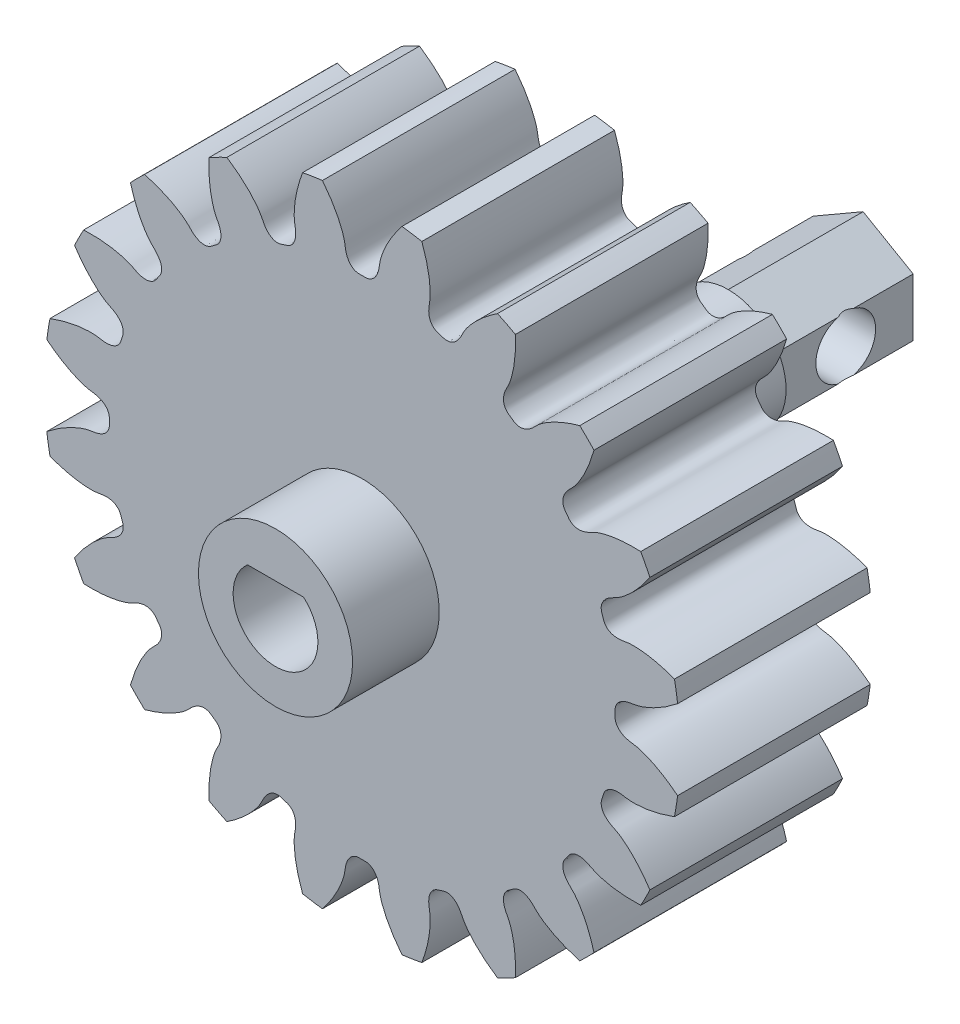
SolidWorks part; units mm, degrees
ref_plane "Front Plane" through (0, 0, 0) normal (0, 0, 1) x (1, 0, 0)
ref_plane "Top Plane" through (0, 0, 0) normal (0, 1, 0) x (1, 0, 0)
ref_plane "Right Plane" through (0, 0, 0) normal (1, 0, 0) x (0, 0, -1)
ref_axis "Axis1" through (0, 0, 55) along (0, 0, -1)
sketch "SketchRevolveSpurAssembly01Pinion" plane through (0, 0, 0) normal (1, 0, 0) x (0, 0, -1)
  line L0 (0, 0) -> (1, 0) construction
  line L1 (-5, 0) -> (-5, 16.5)
  line L2 (-5, 16.5) -> (5, 16.5)
  line L3 (5, 16.5) -> (5, 0)
  line L4 (5, 0) -> (-5, 0)
  dimension "Side1" = 5
  dimension "OutsideRadius" = 16.5
  dimension "Side2" = 5
revolve "SpurAssembly01Pinion" add sketch "SketchRevolveSpurAssembly01Pinion" angle 360 about L0
sketch "SketchToothSpurAssembly01Pinion" plane through (0, 0, 0) normal (0, 0, 1) x (1, 0, 0)
  arc A0 (16.4388, 2.1204) -> (16.4388, -2.1204) centre (0, 0) cw
  spline S0 degree 3 poles (16.4388, -2.1204) (16.3062, -2.0126) (16.1079, -1.8609) (15.8417, -1.6767) (15.6549, -1.5557) (15.4759, -1.4476) (15.3054, -1.3516) (15.1441, -1.2672) (14.9923, -1.1937) (14.8506, -1.1305) (14.7196, -1.0767) (14.5996, -1.0318) (14.491, -0.9949) (14.3942, -0.9653) (14.3096, -0.9423) (14.2375, -0.925) (14.178, -0.9126) (14.0492, -0.8903) (13.9123, -0.8782) (13.7697, -0.8427) (13.6956, -0.8206) (13.6244, -0.795) (13.5557, -0.7654) (13.4893, -0.7311) (13.4248, -0.6913) (13.3623, -0.6446) (13.3021, -0.5892) (13.2452, -0.523) (13.1943, -0.4439) (13.1533, -0.3509) (13.1303, -0.2534) (13.1208, -0.135) (13.1277, 0) (13.1208, 0.135) (13.1303, 0.2534) (13.1533, 0.3509) (13.1943, 0.4439) (13.2452, 0.523) (13.3021, 0.5892) (13.3623, 0.6446) (13.4248, 0.6913) (13.4893, 0.7311) (13.5557, 0.7654) (13.6244, 0.795) (13.6956, 0.8206) (13.7697, 0.8427) (13.9123, 0.8782) (14.0492, 0.8903) (14.178, 0.9126) (14.2375, 0.925) (14.3096, 0.9423) (14.3942, 0.9653) (14.491, 0.9949) (14.5996, 1.0318) (14.7196, 1.0767) (14.8506, 1.1305) (14.9923, 1.1937) (15.1441, 1.2672) (15.3054, 1.3516) (15.4759, 1.4476) (15.6549, 1.5557) (15.8417, 1.6767) (16.1079, 1.8609) (16.3062, 2.0126) (16.4388, 2.1204) knots 0 0 0 0 0.061423 0.08971 0.11638 0.141434 0.164872 0.186693 0.206898 0.225486 0.242459 0.257814 0.271554 0.283677 0.294183 0.303073 0.310347 0.316004 0.350077 0.359568 0.368803 0.377844 0.386769 0.395676 0.404689 0.413963 0.423683 0.434051 0.445256 0.457401 0.47042 0.481067 0.5 0.518933 0.52958 0.542599 0.554744 0.565949 0.576317 0.586037 0.595311 0.604324 0.613231 0.622156 0.631197 0.640432 0.649923 0.683996 0.689653 0.696927 0.705817 0.716323 0.728446 0.742186 0.757541 0.774514 0.793102 0.813307 0.835128 0.858566 0.88362 0.91029 0.938577 1 1 1 1
extrude "ToothExtrudeCutSpurAssembly01Pinion" cut sketch "SketchToothSpurAssembly01Pinion" against normal blind 5 and the other way blind 5
pattern_circular "PatternSpurAssembly01Pinion" count 20 every 18 about axis through (0, 0, 55) along (0, 0, -1) of "ToothExtrudeCutSpurAssembly01Pinion"
sketch "AuxiliarySketchSpurAssembly01Pinion" plane through (0, 0, 0) normal (0, 0, 1) x (1, 0, 0)
  circle A0 centre (0, 0) radius 15 construction
  circle A1 centre (0, 0) radius 14.0954 construction
  circle A2 centre (0, 0) radius 14.1048 construction
  circle A3 centre (0, 0) radius 16.5 construction
  circle A4 centre (0, 0) radius 13.125 construction
  dimension "PitchDiameter" = 30
  dimension "BaseDiameter" = 28.1908
  dimension "FormDiameter" = 28.2095
  dimension "MajorDiameter" = 33
  dimension "MinorDiameter" = 26.25
sketch "Sketch2" plane through (0, 0, -5) normal (0, 0, -1) x (-1, 0, 0)
  circle A0 centre (0, 0) radius 3
extrude "Boss-Extrude1" add sketch "Sketch2" along normal blind 9
sketch "Sketch3" plane through (0, 0, -14) normal (0, 0, -1) x (-1, 0, 0)
  line L0 (0, 3) -> (-2.5981, 1.5)
  line L1 (-2.5981, 1.5) -> (-2.5981, -1.5)
  line L2 (0, -3) -> (0, 3) construction
  line L3 (-2.5981, -1.5) -> (2.5981, 1.5) construction
  line L4 (2.5981, -1.5) -> (-2.5981, 1.5) construction
  line L5 (-2.5981, -1.5) -> (0, -3)
  line L6 (0, -3) -> (2.5981, -1.5)
  line L7 (2.5981, -1.5) -> (2.5981, 1.5)
  line L8 (2.5981, 1.5) -> (0, 3)
  circle A0 centre (0, 0) radius 3 construction
  point P11 (0, 0)
  point P15 (0, 0)
  point P18 (0, 0)
extrude "Boss-Extrude2" add sketch "Sketch3" along normal blind 7
sketch "Sketch4" plane through (2.5981, 0, 0) normal (1, 0, 0) x (0, 0, -1)
  line L0 (14, 1.5) -> (21, -1.5) construction
  circle A0 centre (17.5, 0) radius 1.55
extrude "Cut-Extrude3" cut sketch "Sketch4" against normal up to surface (5.1962 mm away) up to face at (-2.5981, 0, -17.5)
sketch "Sketch5" plane through (0, 0, 5) normal (0, 0, 1) x (1, 0, 0)
  circle A0 centre (0, 0) radius 4
extrude "Boss-Extrude3" add sketch "Sketch5" along normal blind 4.5
sketch "Sketch6" plane through (0, 0, 9.5) normal (0, 0, 1) x (1, 0, 0)
  line L0 (0, 0) -> (0, 1.65) construction
  line L1 (-1.4552, 1.65) -> (1.4552, 1.65)
  circle A0 centre (0, 0) radius 2.2 construction
  arc A1 (1.4552, 1.65) -> (-1.4552, 1.65) centre (0, 0) cw
  point P7 (0, 1.65)
extrude "Cut-Extrude4" cut sketch "Sketch6" against normal blind 8
